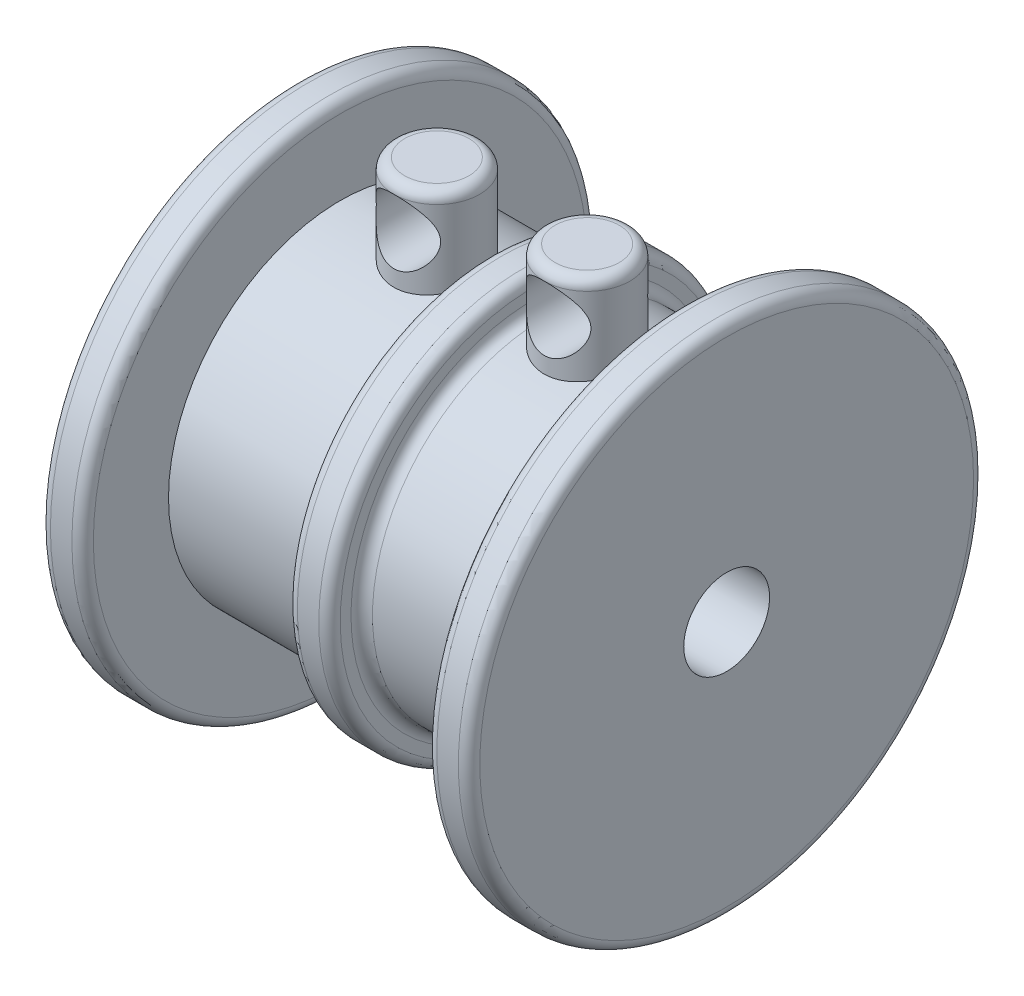
SolidWorks part; units mm, degrees
ref_plane "Front Plane" through (0, 0, 0) normal (0, 0, 1) x (1, 0, 0)
ref_plane "Top Plane" through (0, 0, 0) normal (0, 1, 0) x (1, 0, 0)
ref_plane "Right Plane" through (0, 0, 0) normal (1, 0, 0) x (0, 0, -1)
sketch "Sketch1" plane through (0, 0, 0) normal (1, 0, 0) x (0, 0, -1)
  circle A0 centre (0, 0) radius 4
  dimension "D1" = 8
extrude "Boss-Extrude1" add sketch "Sketch1" along normal blind 8
sketch "Sketch2" plane through (8, 0, 0) normal (1, 0, 0) x (0, 0, -1)
  circle A0 centre (0, 0) radius 6
extrude "Boss-Extrude2" add sketch "Sketch2" along normal blind 1
sketch "Sketch3" plane through (0, 0, 0) normal (-1, 0, 0) x (0, 0, 1)
  circle A0 centre (0, 0) radius 6
extrude "Boss-Extrude3" add sketch "Sketch3" along normal blind 1
sketch "Sketch4" plane through (0, 0, 0) normal (0, 0, 1) x (1, 0, 0)
  line L0 (4, 4) -> (3.5, 4)
  line L1 (8, 4) -> (0, 4) construction
  line L2 (3.5, 4) -> (3.5, 4.75)
  line L3 (3.5, 4.75) -> (4.5, 4.75)
  line L4 (4.5, 4.75) -> (4.5, 4)
  line L5 (4.5, 4) -> (4, 4)
  line L6 (0, 0) -> (8, 0) construction
  line L7 (0, -6) -> (0, 6) construction
  line L8 (8, 6) -> (8, -6) construction
  dimension "D1" = 1
  dimension "D2" = 0.5
  dimension "D3" = 0.75
revolve "Revolve1" add sketch "Sketch4" angle 360 about L6
sketch "Sketch5" plane through (0, 0, 0) normal (0, 1, 0) x (1, 0, 0)
  line L4 (4.5, -4.75) -> (4.5, 4.75) construction
  line L5 (3.5, 4) -> (3.5, -4) construction
  circle A0 centre (2.25, 0) radius 1
  circle A1 centre (5.75, 0) radius 1
  dimension "D1" = 2
  dimension "D2" = 2
  dimension "D3" = 1.25
  dimension "D4" = 1.25
extrude "Boss-Extrude4" add sketch "Sketch5" along normal blind 6
sketch "Sketch6" plane through (0, 0, 0) normal (0, 0, 1) x (1, 0, 0)
  line L0 (3.25, 6) -> (1.25, 6) construction
  line L1 (1.25, 6) -> (1.25, 4) construction
  line L2 (4, 4.75) -> (4, 6.1555) construction
  line L3 (4.5, 4.75) -> (3.5, 4.75) construction
  circle A0 centre (2.25, 5) radius 0.75
  circle A1 centre (5.75, 5) radius 0.75
  dimension "D1" = 1
  dimension "D2" = 1
extrude "Cut-Extrude1" cut sketch "Sketch6" against normal through all both and the other way through all
fillet "Fillet1" radius 0.25 2 edges at (5.75, 6, 1) (2.25, 6, 1)
fillet "Fillet2" radius 0.25 8 edges at (4.5, -4.75, 0) (3.5, -4.75, 0) (0, 0, 6) (-1, 0, 6) (8, 0, -6) (9, 0, -6) (4.5, -4, 0) (3.5, 4, 0)
sketch "Sketch7" plane through (-1, 0, 0) normal (-1, 0, 0) x (0, 0, 1)
  circle A0 centre (0, 0) radius 1
extrude "Cut-Extrude2" cut sketch "Sketch7" against normal through all
